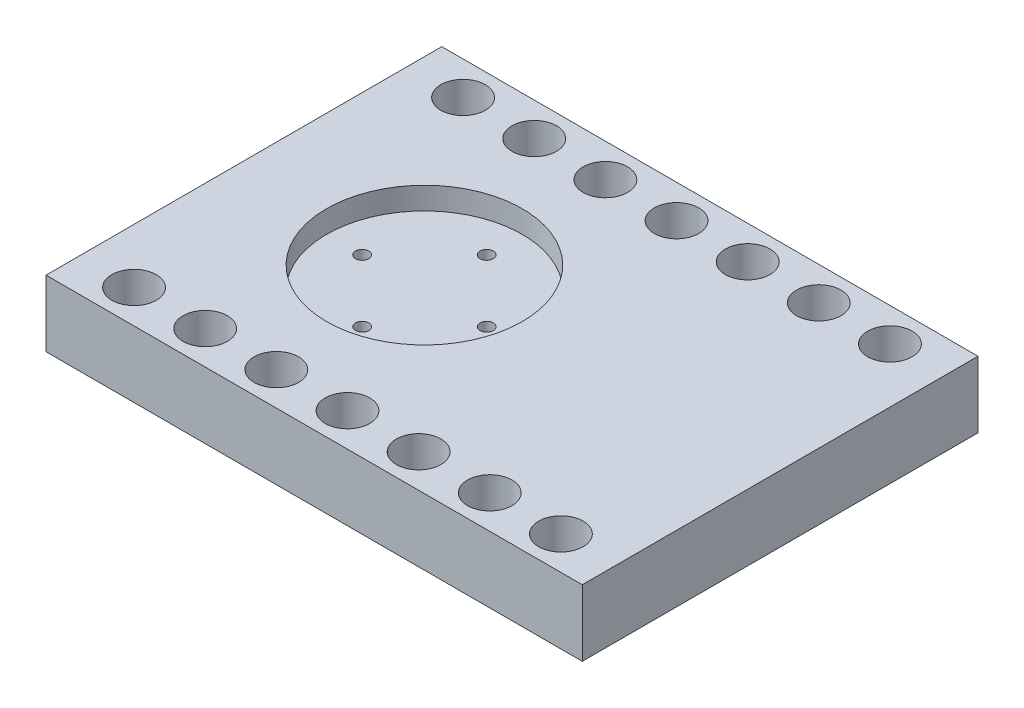
SolidWorks part; units mm, degrees
ref_plane "Front Plane" through (0, 0, 0) normal (0, 0, 1) x (1, 0, 0)
ref_plane "Top Plane" through (0, 0, 0) normal (0, 1, 0) x (1, 0, 0)
ref_plane "Right Plane" through (0, 0, 0) normal (1, 0, 0) x (0, 0, -1)
sketch "Sketch3" plane through (0, 0, 0) normal (0, 1, 0) x (1, 0, 0)
  line L0 (-52.2632, 0) -> (55.5227, 0) construction
  line L1 (0, 43.998) -> (0, -43.557) construction
  line L2 (-9.85, 40.6896) -> (-9.85, -33.1895) construction
  circle A0 centre (-9.85, 0) radius 10 construction
  circle A1 centre (-9.85, 0) radius 7 construction
  circle A2 centre (-9.85, 7) radius 0.75
  circle A3 centre (-16.85, 0) radius 0.75
  circle A4 centre (-9.85, -7) radius 0.75
  circle A5 centre (-2.85, 0) radius 0.75
  line B0 (-34.3973, 0) -> (32.9918, 0) construction
  line B1 (-20.15, 9.75) -> (-20.15, -9.75) construction
  line B2 (20.15, 9.75) -> (20.15, -9.75) construction
  line B3 (-20.15, 9.75) -> (20.15, -9.75) construction
  line B4 (-20.15, -9.75) -> (20.15, 9.75) construction
  line B5 (0, 26.5192) -> (0, -28.2205) construction
  line B6 (-30.15, 22.25) -> (30.15, 22.25)
  line B7 (-30.15, 22.25) -> (-30.15, -22.25)
  line B8 (-30.15, -22.25) -> (30.15, -22.25)
  line B9 (30.15, 22.25) -> (30.15, -22.25)
  line B10 (-27, 9.75) -> (27, 9.75) construction
  line B11 (-27, 9.75) -> (-27, -9.75) construction
  line B12 (-27, -9.75) -> (27, -9.75) construction
  line B13 (27, 9.75) -> (27, -9.75) construction
  line B14 (-27, 9.75) -> (27, -9.75) construction
  line B15 (-27, -9.75) -> (27, 9.75) construction
  dimension "D8" = 1.5
  dimension "D4" = 20
  dimension "D5" = 14
  dimension "D6" = 1.5
  dimension "D7" = 1.5
  dimension "D9" = 1.5
  dimension "D1" = 0
  dimension "D2" = 0
  dimension "D3" = 9.85
sketch_block_instance "Block3-1"
sketch_block "Block3" parameters "D1"=40.3, "D2"=19.5, "D3"=10, "D4"=10, "D5"=54, "D6"=34.5, "D7"=17.25
extrude "Boss-Extrude1" add sketch "Sketch3" along normal blind 7.46
sketch "Sketch4" plane through (0, 7.46, 0) normal (0, 1, 0) x (1, 0, 0)
  line L0 (0, 22.25) -> (0, -22.25) construction
  line L1 (30.15, 22.25) -> (-30.15, 22.25) construction
  line L2 (-30.15, -22.25) -> (30.15, -22.25) construction
  line L3 (-30.15, 0) -> (30.15, 0) construction
  line L4 (-30.15, 22.25) -> (-30.15, -22.25) construction
  line L5 (30.15, -22.25) -> (30.15, 22.25) construction
  line L6 (-9.85, 7) -> (-9.85, -7) construction
  circle A0 centre (-9.85, 0) radius 11
  dimension "D1" = 22
extrude "Cut-Extrude1" cut sketch "Sketch4" against normal blind 2.5
sketch "Sketch5" plane through (0, 7.46, 0) normal (0, 1, 0) x (1, 0, 0)
  line L0 (-30.15, 18.5) -> (30.15, 18.5) construction
  line L1 (-30.15, 22.25) -> (-30.15, -22.25) construction
  line L2 (30.15, -22.25) -> (30.15, 22.25) construction
  line L3 (30.15, 22.25) -> (-30.15, 22.25) construction
  line L4 (-30.15, -18.5) -> (30.15, -18.5) construction
  line L5 (-30.15, -22.25) -> (30.15, -22.25) construction
  line L6 (0, 22.25) -> (0, -22.25) construction
  line L7 (-30.15, 0) -> (30.15, 0) construction
  circle A0 centre (0, 18.5) radius 2.5
  circle A1 centre (8, 18.5) radius 2.5
  circle A2 centre (16, 18.5) radius 2.5
  circle A3 centre (24, 18.5) radius 2.5
  circle A4 centre (-24, 18.5) radius 2.5
  circle A5 centre (-16, 18.5) radius 2.5
  circle A6 centre (-8, 18.5) radius 2.5
  circle A7 centre (-8, -18.5) radius 2.5
  circle A8 centre (-16, -18.5) radius 2.5
  circle A9 centre (-24, -18.5) radius 2.5
  circle A10 centre (24, -18.5) radius 2.5
  circle A11 centre (16, -18.5) radius 2.5
  circle A12 centre (8, -18.5) radius 2.5
  circle A13 centre (0, -18.5) radius 2.5
  dimension "D3" = 5
  dimension "D5" = 8
  dimension "D1" = 3.75
  dimension "D2" = 3.75
  dimension "D4" = 4
extrude "Cut-Extrude2" cut sketch "Sketch5" against normal through all
